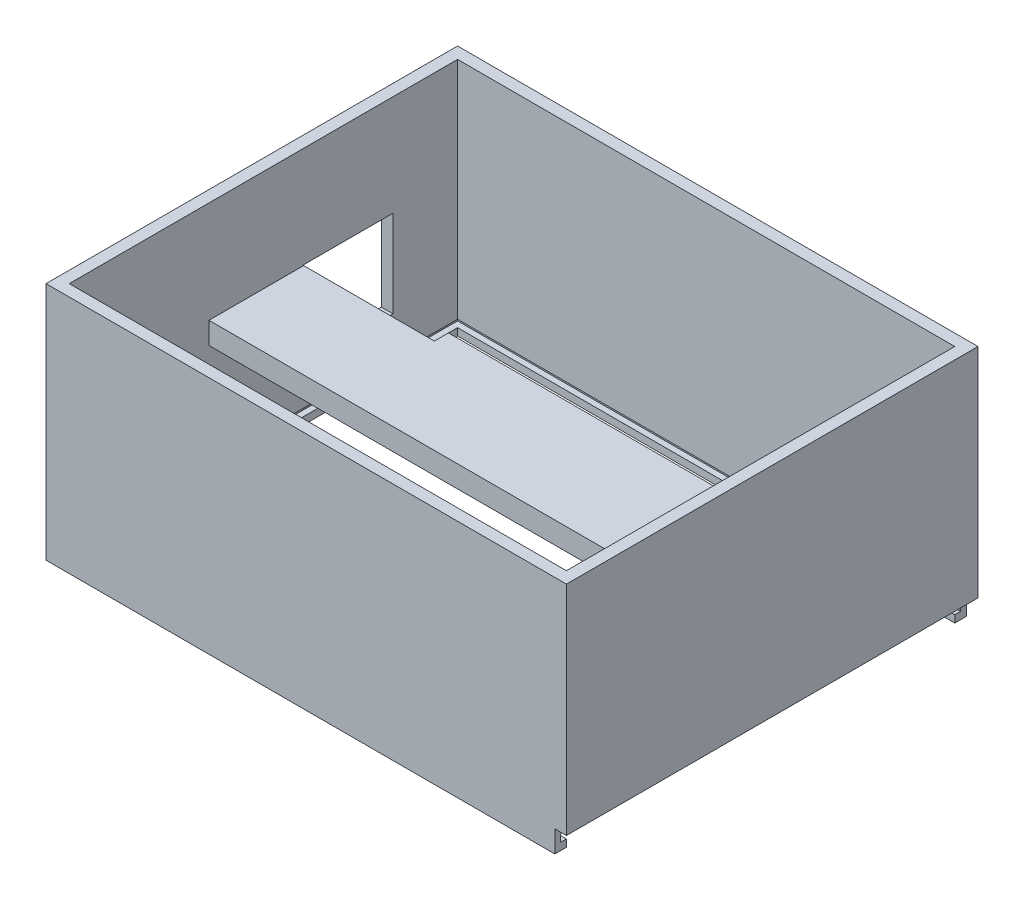
SolidWorks part; units mm, degrees
ref_plane "Front Plane" through (0, 0, 0) normal (0, 0, 1) x (1, 0, 0)
ref_plane "Top Plane" through (0, 0, 0) normal (0, 1, 0) x (1, 0, 0)
ref_plane "Right Plane" through (0, 0, 0) normal (1, 0, 0) x (0, 0, -1)
sketch "Sketch1" plane through (0, 0, 0) normal (0, 1, 0) x (1, 0, 0)
  line L1 (-33.021, -34.9955) -> (35.479, -34.9955)
  line L2 (-33.021, -34.9955) -> (-33.021, 18.5045)
  line L3 (-33.021, 18.5045) -> (35.479, 18.5045)
  line L4 (35.479, -34.9955) -> (35.479, 18.5045)
  line L5 (-34.621, 20.1045) -> (37.079, 20.1045)
  line L6 (-34.621, 20.1045) -> (-34.621, -36.5955)
  line L7 (-34.621, -36.5955) -> (37.079, -36.5955)
  line L8 (37.079, 20.1045) -> (37.079, -36.5955)
  dimension "D1" = 53.5
  dimension "D2" = 68.5
  dimension "D3" = 1.6
  dimension "D4" = 1.6
  dimension "D5" = 1.6
  dimension "D6" = 1.6
extrude "Boss-Extrude1" add sketch "Sketch1" along normal blind 30
sketch "Sketch2" plane through (-33.021, 0, 0) normal (1, 0, 0) x (0, 0, -1)
  line L0 (18.5045, 30) -> (-34.9955, 30) construction
  line L1 (-15.7455, 13) -> (-0.7455, 13)
  line L2 (-15.7455, 13) -> (-15.7455, 16)
  line L3 (-15.7455, 16) -> (-0.7455, 16)
  line L4 (-0.7455, 13) -> (-0.7455, 16)
  point P6 (-8.2455, 30)
  dimension "D1" = 14
  dimension "D2" = 15
  dimension "D3" = 3
  dimension "D4" = 7.5
extrude "Boss-Extrude2" add sketch "Sketch2" along normal blind 70
sketch "Sketch3" plane through (-33.021, 0, 0) normal (1, 0, 0) x (0, 0, -1)
  line L0 (18.5045, 30) -> (18.5045, 0) construction
  line L1 (-2.6955, 4.1) -> (9.6045, 4.1)
  line L2 (-2.6955, 4.1) -> (-2.6955, 16.1)
  line L3 (-2.6955, 16.1) -> (9.6045, 16.1)
  line L4 (9.6045, 4.1) -> (9.6045, 16.1)
  line L5 (18.5045, 0) -> (-34.9955, 0) construction
  line L7 (-31.7955, 4.1) -> (-22.4955, 4.1)
  line L8 (-31.7955, 4.1) -> (-31.7955, 15.1)
  line L9 (-31.7955, 15.1) -> (-22.4955, 15.1)
  line L10 (-22.4955, 4.1) -> (-22.4955, 15.1)
  dimension "D1" = 12.3
  dimension "D2" = 12
  dimension "D3" = 8.9
  dimension "D4" = 4.1
  dimension "D5" = 9.3
  dimension "D6" = 11
  dimension "D7" = 19.8
  dimension "D8" = 4.1
extrude "Cut-Extrude1" cut sketch "Sketch3" against normal blind 1.6
extrude "Cut-Extrude2" cut sketch "Sketch3<2>" along normal blind 18
sketch "Sketch3<2>" plane through (-33.021, 0, 0) normal (1, 0, 0) x (0, 0, -1) same geometry as "Sketch3"
sketch "Sketch4" plane through (0, 0, 0) normal (0, -1, 0) x (1, 0, 0)
  line L0 (35.479, 36.5955) -> (35.479, 34.9955)
  line L1 (-34.621, 36.5955) -> (37.079, 36.5955) construction
  line L2 (-33.021, 34.9955) -> (35.479, 34.9955) construction
  line L3 (35.479, 34.9955) -> (-33.021, 34.9955)
  line L4 (-33.021, 34.9955) -> (-33.021, -18.5045)
  line L5 (-33.021, -18.5045) -> (35.479, -18.5045)
  line L6 (35.479, -18.5045) -> (35.479, -20.1045)
  line L7 (37.079, -20.1045) -> (-34.621, -20.1045) construction
  line L8 (35.479, -20.1045) -> (-34.621, -20.1045)
  line L9 (-34.621, -20.1045) -> (-34.621, 36.5955)
  line L10 (-34.621, 36.5955) -> (35.479, 36.5955)
  dimension "D1" = 0
extrude "Boss-Extrude3" add sketch "Sketch4" along normal blind 3
sketch "Sketch5" plane through (35.479, 0, 0) normal (1, 0, 0) x (0, 0, -1)
  line L0 (-34.9955, -3) -> (-36.5955, -3) construction
  line L1 (-35.7955, -1) -> (19.3045, -1)
  line L2 (-35.7955, -1) -> (-35.7955, -2)
  line L3 (-35.7955, -2) -> (19.3045, -2)
  line L4 (19.3045, -1) -> (19.3045, -2)
  line L5 (-34.9955, 0) -> (-36.5955, 0) construction
  line L6 (-36.5955, -3) -> (-36.5955, 0) construction
  line L7 (20.1045, -3) -> (20.1045, 0) construction
  dimension "D1" = 1
  dimension "D2" = 1
  dimension "D3" = 0.8
  dimension "D4" = 0.8
extrude "Cut-Extrude3" cut sketch "Sketch5" against normal blind 69.3
